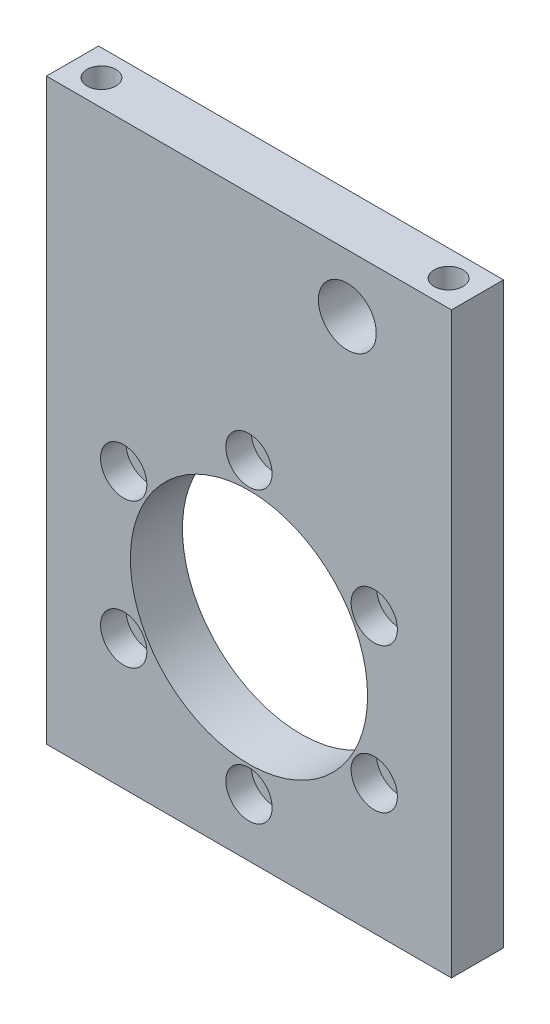
SolidWorks part; units mm, degrees
material "1060 Alloy"
ref_plane "Front Plane" through (0, 0, 0) normal (0, 0, 1) x (1, 0, 0)
ref_plane "Top Plane" through (0, 0, 0) normal (0, 1, 0) x (1, 0, 0)
ref_plane "Right Plane" through (0, 0, 0) normal (1, 0, 0) x (0, 0, -1)
sketch "Sketch1" plane through (0, 0, 0) normal (0, 0, 1) x (1, 0, 0)
  line L1 (0, 0) -> (70, 0)
  line L2 (0, 0) -> (0, 100)
  line L3 (0, 100) -> (70, 100)
  line L4 (70, 0) -> (70, 100)
  dimension "D1" = 70
  dimension "D2" = 100
extrude "Boss-Extrude1" add sketch "Sketch1" along normal mid plane 9
sketch "Sketch3" plane through (0, 0, 0) normal (0, 0, 1) x (1, 0, 0)
  circle A0 centre (35, 35) radius 20.5
  dimension "D1" = 41
  dimension "D2" = 35
  dimension "D3" = 35
extrude "Cut-Extrude2" cut sketch "Sketch3" against normal through all both and the other way through all
hole_wizard "M6 Tapped Hole1" positions "Sketch4" profile "Sketch5" tap size "M6" standard "ISO"
sketch "Sketch4" plane through (0, 0, 0) normal (0, -1, 0) x (-1, 0, 0)
  line L0 (-70, -4.5) -> (-70, 4.5) construction
  line L1 (0, -4.5) -> (0, 4.5) construction
  point P0 (-65, 0)
  point P2 (-5, 0)
  dimension "D1" = 5
  dimension "D2" = 5
sketch "Sketch5" plane through (65, 0, 0) normal (1, 0, 0) x (0, 0, -1)
  line L0 (0, 0) -> (0, 16.5022)
  line L1 (0, 16.5022) -> (2.5, 15)
  line L2 (2.5, 15) -> (2.5, 0)
  line L5 (2.5, 0) -> (0, 0)
  line L10 (0, 16.5022) -> (-2.5, 15) construction
  line L11 (0, -6.35) -> (0, 107.95) construction
  dimension "Tap Drill Dia." = 5
  dimension "Tap Drill Depth" = 15
  dimension "Drill Angle" = 118
cosmetic thread "Hole Thread1" parameters "D1"=12, "D2"=6
cosmetic thread "Hole Thread2" parameters "D1"=12, "D2"=6
ref_plane "Plane1" through (0, 50, 0) normal (0, 1, 0) x (1, 0, 0)
mirror "Mirror1" about plane through (0, 50, 0) normal (0, 1, 0) of "M6 Tapped Hole1"
hole_wizard "CBORE for M4 Hex Socket Head Cap Screw1" positions "Sketch6" profile "Sketch7" counterbore size "M4" standard "ISO" end condition through all
sketch "Sketch6" plane through (0, 0, 4.5) normal (0, 0, 1) x (1, 0, 0)
  line L0 (14.5, 35) -> (55.5, 35) construction
  circle A0 centre (35, 35) radius 20.5 construction
  point P0 (35, 60)
  point P16 (35, 35)
  dimension "D1" = 25
sketch "Sketch7" plane through (35, 60, 4.5) normal (1, 0, 0) x (0, -1, 0)
  line L0 (0, 0) -> (0, 9)
  line L1 (0, 9) -> (2.15, 9)
  line L3 (2.15, 9) -> (2.15, 4.4)
  line L4 (2.15, 4.4) -> (4, 4.4)
  line L5 (4, 4.4) -> (4, 0)
  line L7 (4, 0) -> (0, 0)
  line L11 (0, -6.35) -> (0, 107.95) construction
  dimension "Thru Hole Dia." = 4.3
  dimension "Thru Hole Depth" = 9
  dimension "C'Bore Dia." = 8
  dimension "C'Bore Depth" = 4.4
pattern_circular "CirPattern1" count 6 over 360 about axis through (35, 35, -4.5) along (0, 0, 1) of "CBORE for M4 Hex Socket Head Cap Screw1"
sketch "Sketch8" plane through (0, 0, 4.5) normal (0, 0, 1) x (1, 0, 0)
  line L0 (70, 100) -> (0, 100) construction
  line L1 (70, 0) -> (70, 100) construction
  circle A0 centre (52, 90) radius 5
  dimension "D1" = 10
  dimension "D2" = 10
  dimension "D3" = 18
extrude "Cut-Extrude3" cut sketch "Sketch8" against normal blind 10
